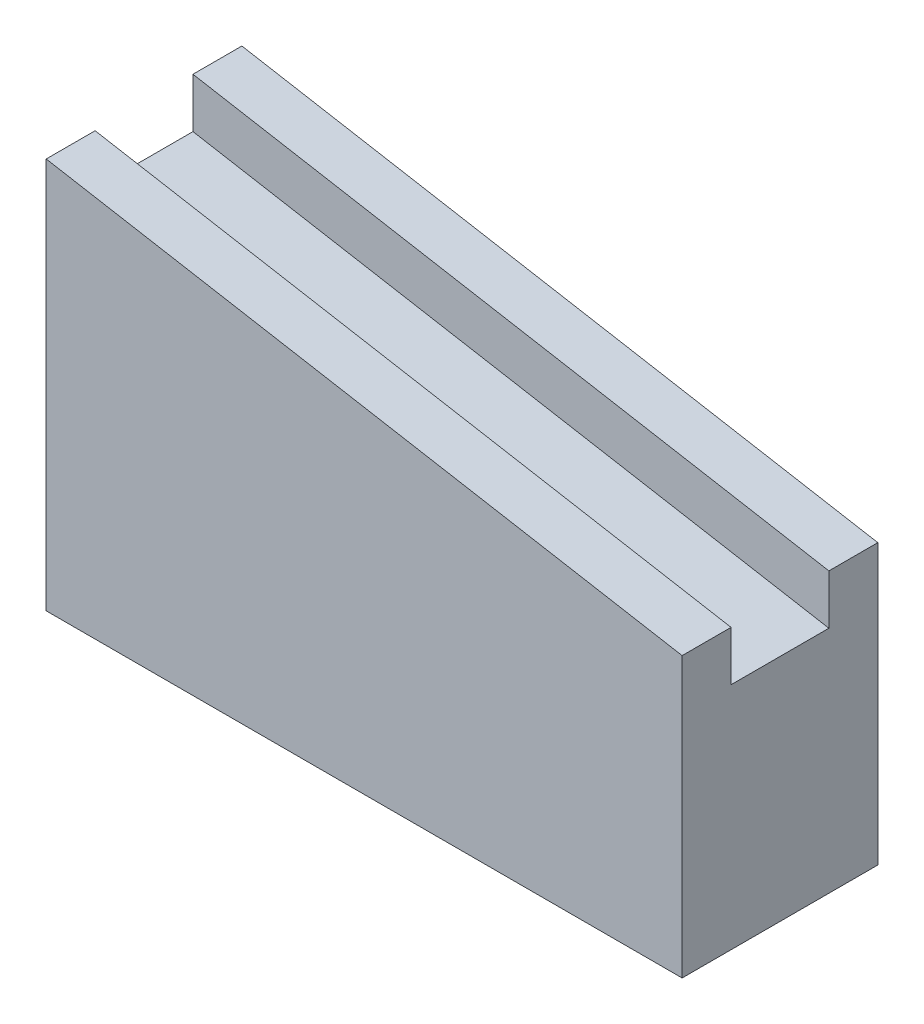
SolidWorks part; units mm, degrees
ref_plane "Plano frontal" through (0, 0, 0) normal (0, 0, 1) x (1, 0, 0)
ref_plane "Plano superior" through (0, 0, 0) normal (0, 1, 0) x (1, 0, 0)
ref_plane "Plano direito" through (0, 0, 0) normal (1, 0, 0) x (0, 0, -1)
sketch "Esboço1" plane through (0, 0, 0) normal (0, 0, 1) x (1, 0, 0)
  line L0 (-53.2953, 9.3008) -> (76.7047, 9.3008)
  line L1 (-53.2953, 9.3008) -> (-53.2953, 89.3008)
  line L2 (76.7047, 9.3008) -> (76.7047, 66.3783)
  line L3 (-53.2953, 89.3008) -> (76.7047, 66.3783)
  dimension "D1" = 100
  dimension "D2" = 80
  dimension "D3" = 130
extrude "Ressalto-extrusão1" add sketch "Esboço1" along normal blind 40
sketch "Esboço3" plane through (13.6643, 77.494, 0) normal (0.1736, 0.9848, 0) x (0.9848, -0.1736, 0)
  line L0 (64.0129, -40) -> (-67.9926, -40) construction
  line L1 (-71.0201, -30) -> (70.4962, -30)
  line L2 (-71.0201, -30) -> (-71.0201, -10)
  line L3 (-71.0201, -10) -> (70.4962, -10)
  line L4 (70.4962, -30) -> (70.4962, -10)
  line L5 (64.0129, 0) -> (-67.9926, 0) construction
  dimension "D1" = 10
  dimension "D2" = 10
extrude "Corte-extrusão2" cut sketch "Esboço3" against normal blind 10
